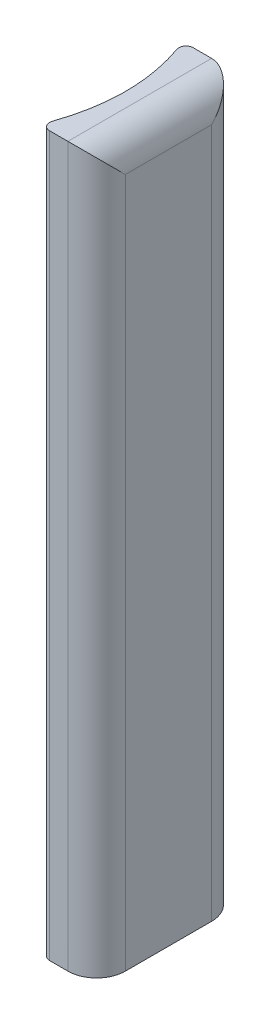
SolidWorks part; units mm, degrees
material "PET"
ref_plane "Front Plane" through (0, 0, 0) normal (0, 0, 1) x (1, 0, 0)
ref_plane "Top Plane" through (0, 0, 0) normal (0, 1, 0) x (1, 0, 0)
ref_plane "Right Plane" through (0, 0, 0) normal (1, 0, 0) x (0, 0, -1)
sketch "Sketch1" plane through (0, 0, 0) normal (0, 0, 1) x (1, 0, 0)
  line L1 (-2, -25) -> (2, -25)
  line L2 (-2, -25) -> (-2, 25)
  line L3 (-2, 25) -> (2, 25)
  line L4 (2, -25) -> (2, 25)
  line L5 (-2, -25) -> (2, 25) construction
  line L6 (-2, 25) -> (2, -25) construction
  point P0 (0, 0)
  dimension "D1" = 4
  dimension "D2" = 50
extrude "Boss-Extrude1" add sketch "Sketch1" along normal blind 5 and the other way blind 5
sketch "Sketch2" plane through (0, 25, 0) normal (0, 1, 0) x (1, 0, 0)
  line L0 (-2, 0) -> (-1, 0)
  line L1 (-2, -5) -> (-2, 5) construction
  line L2 (-2, -5) -> (-2, 5)
  spline S0 degree 2 poles (-2, 5) (0, 0) (-2, -5) knots 0 0 0 1 1 1
  line M2 (-2, 5) -> (-2, -5)
  dimension "D1" = 1
extrude "Cut-Extrude1" cut sketch "Sketch2" against normal blind 60 contours S0 L0 M2 | S0 L0 M2 region at (-1.6, 25, -1.875) region at (-1.6, 25, 1.875)
fillet "Fillet2" radius 2 3 edges at (2, 0, -5) (2, 25, 0) (2, 0, 5)
fillet "Fillet3" radius 0.5 2 edges
